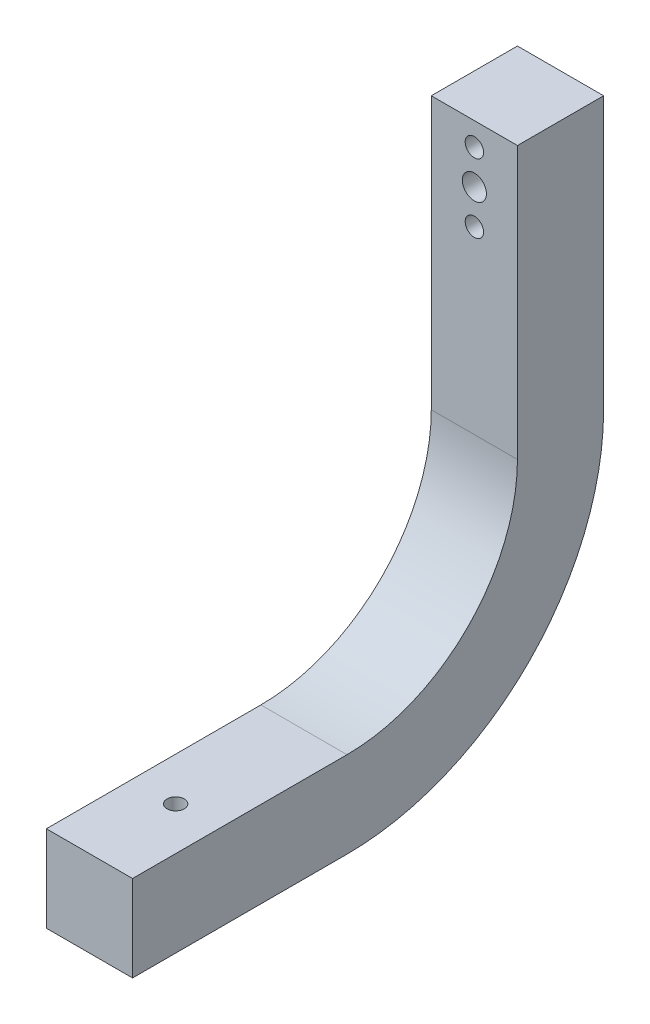
SolidWorks part; units mm, degrees
ref_plane "Front Plane" through (0, 0, 0) normal (0, 0, 1) x (1, 0, 0)
ref_plane "Top Plane" through (0, 0, 0) normal (0, 1, 0) x (1, 0, 0)
ref_plane "Right Plane" through (0, 0, 0) normal (1, 0, 0) x (0, 0, -1)
ref_axis "Z" through (0, 0, 86.1) along (0, 0, -1)
sketch "Sketch1" plane through (0, 0, 0) normal (1, 0, 0) x (0, 0, -1)
  line L0 (-15, 10) -> (0, 10)
  line L1 (0, 10) -> (0, -37.3333)
  line L2 (0, -32) -> (-50, -82) construction
  line L3 (-44.6667, -82) -> (-67, -82)
  line L4 (-67, -82) -> (-67, -67) construction
  line L5 (-67, -67) -> (-44.6667, -67)
  line L6 (-56.2132, -67) -> (-15, -25.7868) construction
  line L7 (-15, -37.3333) -> (-15, 10)
  line L8 (-35.6066, -46.3934) -> (-25, -57) construction
  line L9 (-44.6667, -67) -> (-56.2132, -67) construction
  line L10 (-67, -67) -> (-82, -67)
  line L11 (-67, -67) -> (-67, -82) construction
  line L12 (-67, -82) -> (-82, -82)
  line L13 (-82, -67) -> (-82, -82)
  line L14 (-15, -25.7868) -> (-15, -37.3333) construction
  line L15 (0, -37.3333) -> (0, -32) construction
  line L16 (-50, -82) -> (-44.6667, -82) construction
  arc A0 (-44.6667, -67) -> (-15, -37.3333) centre (-44.6667, -37.3333) ccw
  arc A1 (-44.6667, -82) -> (0, -37.3333) centre (-44.6667, -37.3333) ccw
  dimension "D1" = 15
  dimension "D2" = 67
  dimension "D3" = 82
  dimension "D4" = 10
  dimension "D5" = 135
  dimension "D6" = 50
  dimension "D7" = 15
  dimension "D8" = 22.3333
extrude "Boss-Extrude1" add sketch "Sketch1" along normal blind 7.5 and the other way blind 7.5
sketch "Sketch3" plane through (0, -67, 0) normal (0, 1, 0) x (1, 0, 0)
  line L0 (-8.25, 0) -> (8.25, 0) construction
  line L1 (0, -45.1) -> (0, 45.1) construction
  circle A0 centre (0, -67) radius 1.5
  dimension "D2" = 3
  dimension "D1" = 67
extrude "Cut-Extrude1" cut sketch "Sketch3" against normal through all
sketch "Sketch4" plane through (0, 0, 15) normal (0, 0, 1) x (1, 0, 0)
  line L0 (0, -6) -> (0, 6) construction
  circle A0 centre (0, 0) radius 2.1
  circle A1 centre (0, 6) radius 1.6
  circle A2 centre (0, -6) radius 1.6
  dimension "D1" = 4.2
  dimension "D3" = 3.2
  dimension "D2" = 12
extrude "Cut-Extrude2" cut sketch "Sketch4" against normal through all both and the other way through all
ref_axis "Axis1" through (0, -67, 67) along (0, 1, 0)
sketch "Sketch5" plane through (0, -82, 0) normal (0, -1, 0) x (1, 0, 0)
  circle A0 centre (0, 67) radius 2.275
  dimension "D1" = 4.55
extrude "Cut-Extrude3" cut sketch "Sketch5" against normal blind 6
sketch "Sketch6" plane through (0, -82, 0) normal (0, -1, 0) x (1, 0, 0)
  circle A0 centre (0, 67) radius 3.825
  dimension "D1" = 7.65
extrude "Cut-Extrude4" cut sketch "Sketch6" against normal blind 0.75
equation "\"rbracket-width\"= \"L2Thickness\""
equation "\"D1@Boss-Extrude1\"=\"rbracket-width\"/2"
equation "\"D2@Boss-Extrude1\"=\"rbracket-width\"/2"
equation "\"EyeCaptureRadius\"= ( \"EyeDiameter\" + \"EyeClearance\" ) / 2"
equation "\"rbracket_planetocenterline_dist\"= \"BasePlaneDistance\""
equation "\"D2@Sketch1\"=\"rbracket_planetocenterline_dist\""
equation "\"EyeDiameter\" = 100"
equation "\"BasePlaneDistance\" = \"EyeDiameter\"/2+\"L2Thickness\"+\"EyeClearance\""
equation "\"EyeClearance\" = 2"
equation "\"D1@Sketch1\"=\"rbracket-width\""
equation "\"D3@Sketch1\"=(\"EyeDiameter\"+\"EyeClearance\"+\"EyeClearance\")/2 + \"L2Thickness\" + \"rbracket-width\""
equation "\"D4@Sketch1\"= 10"
equation "\"D6@Sketch1\"=\"EyeDiameter\"/2"
equation "\"D7@Sketch1\"=\"rbracket-width\""
equation "\"D1@Sketch3\"=\"BasePlaneDistance\""
equation "\"L2Thickness\" = 15"
equation "\"D8@Sketch1\"=\"rbracket_planetocenterline_dist\"/3"
equation "\"BearingFlangeOD\"= 7.5"
equation "\"BearingFlangeThickness\"= 0.75"
equation "\"BearingHousingID\"=4.5"
equation "\"BearingDepth\"= 6"
equation "\"D1@Sketch5\"=\"BearingHousingID\" + \"PrinterFilamentThickness\" * \"ApplyPrinterOffsets\" / 2"
equation "\"D1@Cut-Extrude3\"=\"BearingDepth\""
equation "\"D1@Sketch6\"=\"BearingFlangeOD\" + \"PrinterFilamentThickness\" * 1.5 * \"ApplyPrinterOffsets\""
equation "\"D1@Cut-Extrude4\"=\"BearingFlangeThickness\""
equation "\"PrinterFilamentThickness\"= 0.1"
equation "\"ApplyPrinterOffsets\"= 1"
